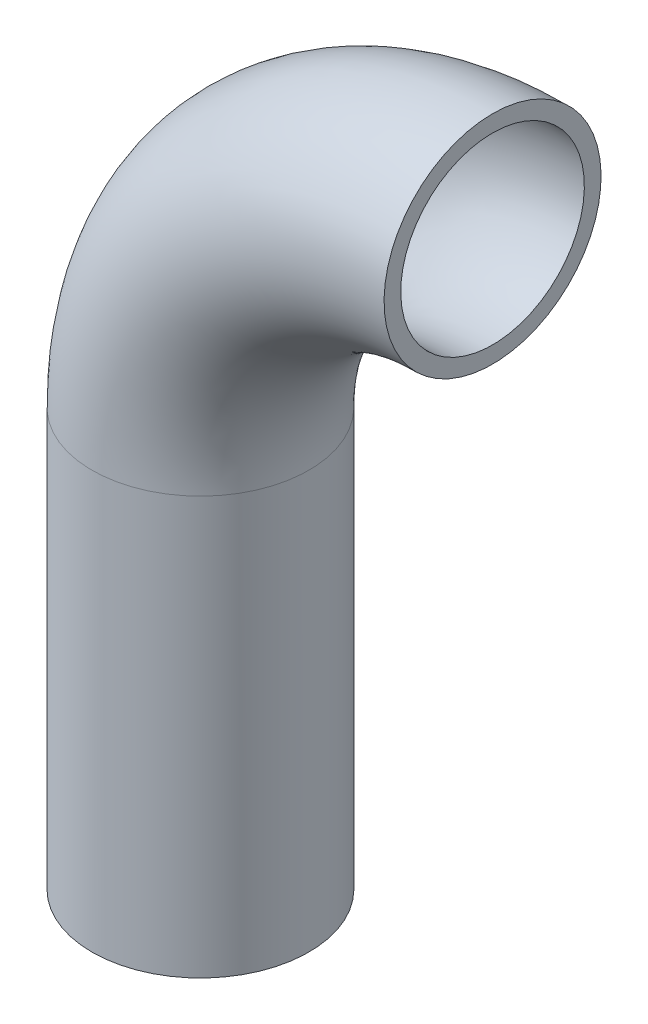
SolidWorks part; units mm, degrees
ref_plane "Front Plane" through (0, 0, 0) normal (0, 0, 1) x (1, 0, 0)
ref_plane "Top Plane" through (0, 0, 0) normal (0, 1, 0) x (1, 0, 0)
ref_plane "Right Plane" through (0, 0, 0) normal (1, 0, 0) x (0, 0, -1)
sketch "Sketch1" plane through (0, 0, 0) normal (0, 1, 0) x (1, 0, 0)
  circle A0 centre (0, 0) radius 13
  dimension "D1" = 26
sketch "Sketch2" plane through (0, 0, 0) normal (0, 0, 1) x (1, 0, 0)
  line L0 (0, 0) -> (0, 50)
  line L1 (0, 50) -> (56.6977, 50) construction
  line L2 (35, 85) -> (35, 30.1106) construction
  arc A0 (0, 50) -> (35, 85) centre (35, 50) cw
  dimension "D1" = 50
  dimension "D2" = 35
sweep "Sweep1" add profiles "Sketch1" path "Sketch2"
sketch "Sketch3" plane through (0, 0, 0) normal (0, 1, 0) x (1, 0, 0)
  circle A0 centre (0, 0) radius 11
  dimension "D1" = 22
sweep "Cut-Sweep1" cut profiles "Sketch3" path "Sketch2<2>"
sketch "Sketch2<2>" plane through (0, 0, 0) normal (0, 0, 1) x (1, 0, 0) same geometry as "Sketch2"
